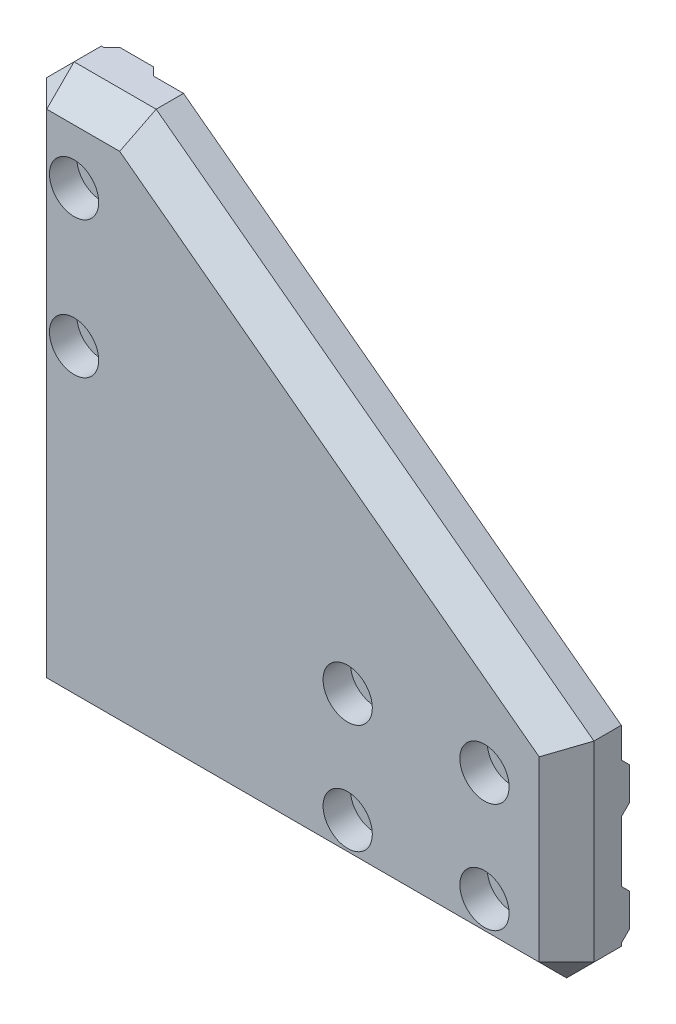
SolidWorks part; units mm, degrees
ref_plane "Płaszczyzna przednia" through (0, 0, 0) normal (0, 0, 1) x (1, 0, 0)
ref_plane "Płaszczyzna górna" through (0, 0, 0) normal (0, 1, 0) x (1, 0, 0)
ref_plane "Płaszczyzna prawa" through (0, 0, 0) normal (1, 0, 0) x (0, 0, -1)
sketch "Sketch1" plane through (0, 0, 0) normal (0, 0, 1) x (1, 0, 0)
  line L0 (0, 0) -> (100, 0)
  line L1 (100, 0) -> (100, 40)
  line L2 (100, 40) -> (20, 100)
  line L3 (20, 100) -> (0, 100)
  line L4 (0, 100) -> (0, 0)
  line L5 (10, 100) -> (10, 0) construction
  line L6 (30, 100) -> (30, 0) construction
  line L8 (100, 30) -> (0, 30) construction
  dimension "D1" = 20
  dimension "D2" = 40
  dimension "D3" = 100
extrude "Boss-Extrude1" add sketch "Sketch1" along normal blind 10
sketch "Sketch2" plane through (0, 0, 0) normal (0, 0, 1) x (1, 0, 0)
  line L5 (10, 100) -> (10, 0) construction
  line L7 (100, 10) -> (0, 10) construction
  line L8 (100, 30) -> (0, 30) construction
  line L9 (0, 0) -> (100, 0) construction
  line L10 (0, 100) -> (0, 0) construction
  line L11 (100, 0) -> (100, 40) construction
  line L12 (0, 100) -> (0, 0) construction
  line L13 (20, 100) -> (0, 100) construction
  line L14 (0, 0) -> (100, 0) construction
  circle A0 centre (10, 85) radius 2.6
  circle A2 centre (10, 60) radius 2.6
  circle A4 centre (85, 30) radius 2.6
  circle A5 centre (85, 10) radius 2.6
  circle A6 centre (60, 10) radius 2.6
  circle A7 centre (60, 30) radius 2.6
  dimension "D9" = 60
  dimension "D1" = 10
  dimension "D2" = 10
  dimension "D4" = 15
  dimension "D6" = 60
  dimension "D7" = 15
  dimension "D8" = 20
extrude "Cut-Extrude1" cut sketch "Sketch2" along normal through all
sketch "Sketch3" plane through (0, 0, 0) normal (0, 0, 1) x (1, 0, 0)
  line L0 (0, 100) -> (0, 0) construction
  line L1 (100, 0) -> (100, 40) construction
  line L2 (100, 25.5) -> (40, 25.5)
  line L3 (100, 25.5) -> (100, 34.5)
  line L4 (100, 34.5) -> (40, 34.5)
  line L5 (40, 25.5) -> (40, 34.5)
  line L6 (20, 100) -> (0, 100) construction
  line L7 (100, 5.5) -> (40, 5.5)
  line L8 (100, 5.5) -> (100, 14.5)
  line L9 (100, 14.5) -> (40, 14.5)
  line L10 (40, 5.5) -> (40, 14.5)
  line L11 (14.5, 100) -> (5.5, 100)
  line L12 (14.5, 100) -> (14.5, 40)
  line L13 (14.5, 40) -> (5.5, 40)
  line L14 (5.5, 100) -> (5.5, 40)
  line L15 (0, 0) -> (100, 0) construction
  circle A0 centre (60, 30) radius 2.6 construction
  circle A1 centre (60, 10) radius 2.6 construction
  circle A3 centre (10, 60) radius 2.6 construction
  dimension "D3" = 4.5
  dimension "D6" = 4.5
  dimension "D10" = 4.5
  dimension "D1" = 40
  dimension "D2" = 40
  dimension "D4" = 9
  dimension "D5" = 9
  dimension "D8" = 9
  dimension "D11" = 40
extrude "Boss-Extrude3" add sketch "Sketch3" against normal blind 1.46 from surface starting at face at (12.6, 85, 0)
extrude "Cut-Extrude2" cut sketch "Sketch2<2>" along normal through all both and the other way through all
sketch "Sketch2<2>" plane through (0, 0, 0) normal (0, 0, 1) x (1, 0, 0) same geometry as "Sketch2"
chamfer "Chamfer1" distance 1.46 angle 45 6 edges at (14.5, 70, -1.46) (5.5, 70, -1.46) (70, 5.5, -1.46) (70, 14.5, -1.46) (70, 25.5, -1.46) (70, 34.5, -1.46)
sketch "Sketch4" plane through (0, 0, 0) normal (0, 0, 1) x (1, 0, 0)
  circle A0 centre (10, 85) radius 4.5
  circle A3 centre (10, 60) radius 4.5
  circle A4 centre (60, 30) radius 4.5
  circle A5 centre (85, 30) radius 4.5
  circle A6 centre (85, 10) radius 4.5
  circle A7 centre (60, 10) radius 4.5
  dimension "D1" = 9
extrude "Cut-Extrude3" cut sketch "Sketch4" against normal blind 5 from surface starting at face at (12.6, 85, 10)
chamfer "Chamfer2" distance 5 angle 45 8 edges at (0, 100, 5) (100, 0, 5) (0, 0, 5) (50, 0, 10) (100, 20, 10) (60, 70, 10) (10, 100, 10) (0, 50, 10)
